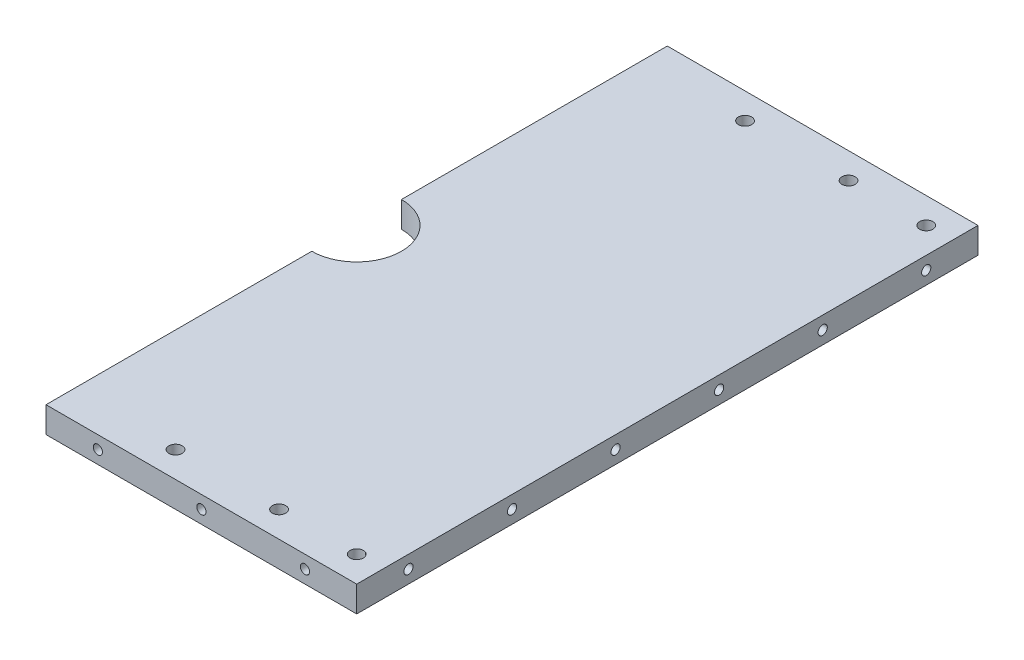
SolidWorks part; units mm, degrees
material "Copper"
ref_plane "Front Plane" through (0, 0, 0) normal (0, 0, 1) x (1, 0, 0)
ref_plane "Top Plane" through (0, 0, 0) normal (0, 1, 0) x (1, 0, 0)
ref_plane "Right Plane" through (0, 0, 0) normal (1, 0, 0) x (0, 0, -1)
sketch "Sketch1" plane through (0, 0, 0) normal (0, 1, 0) x (1, 0, 0)
  line L0 (0, -11) -> (0, -76.2)
  line L1 (0, 76.2) -> (76.22, 76.2)
  line L2 (0, 76.2) -> (0, 11)
  line L3 (0, -76.2) -> (76.22, -76.2)
  line L4 (76.22, 76.2) -> (76.22, -76.2)
  line L5 (0, 0) -> (76.22, 0) construction
  arc A0 (0, -11) -> (0, 11) centre (0, 0) ccw
  circle A1 centre (69.87, 69.85) radius 1.6319
  circle A2 centre (69.87, -69.85) radius 1.6319
  circle A3 centre (50.82, 69.85) radius 1.6319
  circle A4 centre (25.42, 69.85) radius 1.6319
  circle A5 centre (50.82, -69.85) radius 1.6319
  circle A6 centre (25.42, -69.85) radius 1.6319
  dimension "D1" = 11
  dimension "D4" = 3.2639
  dimension "D2" = 76.22
  dimension "D3" = 152.4
  dimension "D5" = 6.35
  dimension "D6" = 6.35
  dimension "D7" = 25.4
  dimension "D8" = 19.05
extrude "Boss-Extrude1" add sketch "Sketch1" along normal blind 6.35
hole_wizard "#4-40 Tapped Hole1" positions "3DSketch1" profile "Sketch2" tap size "#4-40" standard "ANSI Inch"
sketch3d "3DSketch1"
  line L0 (76.22, 6.35, 76.2) -> (76.22, 6.35, -76.2) construction
  line L2 (76.22, 6.35, 76.2) -> (76.22, 0, 76.2) construction
  point P0 (76.22, 3.175, 63.5)
  dimension "D1" = 3.175
  dimension "D2" = 12.7
sketch "Sketch2" plane through (76.22, 3.175, 63.5) normal (0, 1, 0) x (0, 0, -1)
  line L0 (0, 0) -> (0, 8.2792)
  line L1 (0, 8.2792) -> (1.1303, 7.6)
  line L2 (1.1303, 7.6) -> (1.1303, 0)
  line L5 (1.1303, 0) -> (0, 0)
  line L10 (0, 8.2792) -> (-1.1303, 7.6) construction
  line L11 (0, -6.35) -> (0, 107.95) construction
  dimension "Tap Drill Dia." = 2.2606
  dimension "Tap Drill Depth" = 7.6
  dimension "Drill Angle" = 118
cosmetic thread "Hole Thread1"
pattern_linear "LPattern1" count 6 spacing 25.4 along (0, 0, -1) of "#4-40 Tapped Hole1"
cosmetic thread "Hole Thread2"
cosmetic thread "Hole Thread3"
cosmetic thread "Hole Thread4"
cosmetic thread "Hole Thread5"
cosmetic thread "Hole Thread6"
hole_wizard "#4-40 Tapped Hole2" positions "3DSketch2" profile "Sketch3" tap size "#4-40" standard "ANSI Inch"
sketch3d "3DSketch2"
  line L0 (0, 6.35, 76.2) -> (76.22, 6.35, 76.2) construction
  line L1 (76.22, 6.35, 76.2) -> (76.22, 0, 76.2) construction
  point P0 (63.52, 3.175, 76.2)
  dimension "D1" = 3.175
  dimension "D2" = 12.7
sketch "Sketch3" plane through (63.52, 3.175, 76.2) normal (1, 0, 0) x (0, -1, 0)
  line L0 (0, 0) -> (0, 8.2792)
  line L1 (0, 8.2792) -> (1.1303, 7.6)
  line L2 (1.1303, 7.6) -> (1.1303, 0)
  line L5 (1.1303, 0) -> (0, 0)
  line L10 (0, 8.2792) -> (-1.1303, 7.6) construction
  line L11 (0, -6.35) -> (0, 107.95) construction
  dimension "Tap Drill Dia." = 2.2606
  dimension "Tap Drill Depth" = 7.6
  dimension "Drill Angle" = 118
cosmetic thread "Hole Thread7"
pattern_linear "LPattern2" count 3 spacing 25.4 along (-1, 0, 0) of "#4-40 Tapped Hole2"
cosmetic thread "Hole Thread8"
cosmetic thread "Hole Thread9"
ref_plane "Plane1" through (0, 0, 0) normal (0, 0, 1) x (1, 0, 0)
mirror "Mirror1" about plane through (0, 0, 0) normal (0, 0, 1) of "LPattern2"
cosmetic thread "Hole Thread10"
cosmetic thread "Hole Thread11"
cosmetic thread "Hole Thread12"
equation "\"D6@Sketch1\"=\"D5@Sketch1\""
